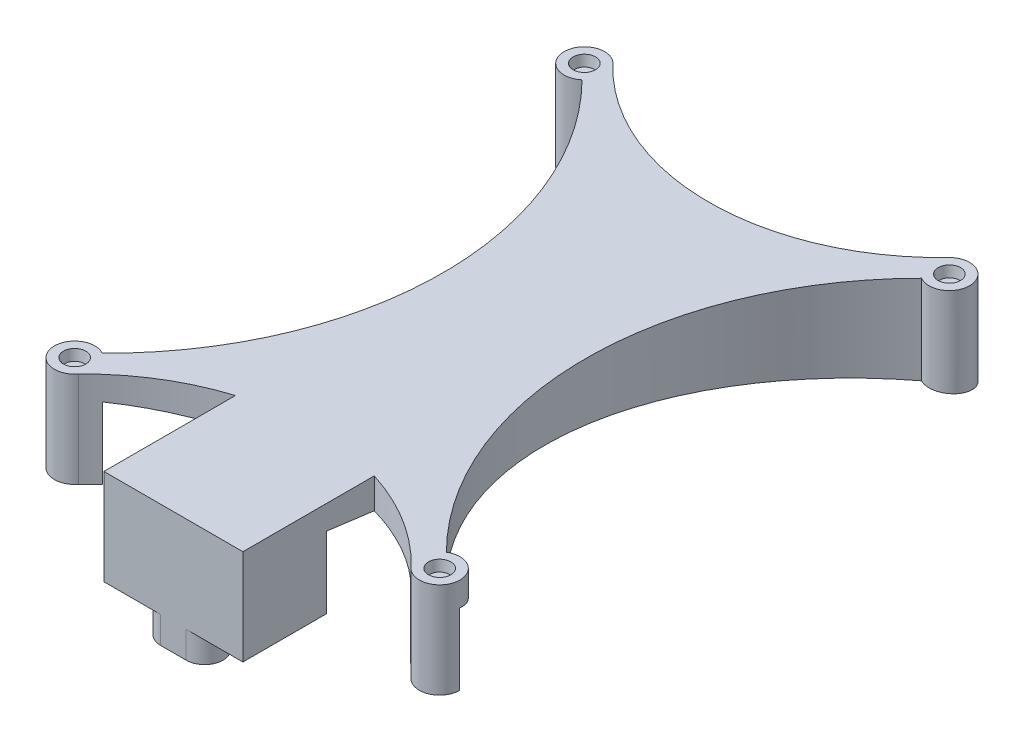
SolidWorks part; units mm, degrees
ref_plane "Front Plane" through (0, 0, 0) normal (0, 0, 1) x (1, 0, 0)
ref_plane "Top Plane" through (0, 0, 0) normal (0, 1, 0) x (1, 0, 0)
ref_plane "Right Plane" through (0, 0, 0) normal (1, 0, 0) x (0, 0, -1)
sketch "Sketch1" plane through (0, 0, 0) normal (0, 1, 0) x (1, 0, 0)
  line L2 (-16.4891, 8.3083) -> (-16.4891, -14.4005)
  line L3 (-16.4891, -14.4005) -> (7.5109, -14.4005)
  line L4 (7.5109, 8.2805) -> (7.5109, -14.4005)
  line L5 (-4.5332, -29.8631) -> (7.5109, -14.4005) construction
  line L6 (-16.4891, -14.4005) -> (-4.5332, -29.8631) construction
  circle A0 centre (-36.0381, 88.0995) radius 1.935 construction
  circle A1 centre (26.9839, 88.0995) radius 1.935 construction
  circle A2 centre (-36.0381, 0.0995) radius 1.935 construction
  circle A3 centre (26.9839, 0.0995) radius 1.935 construction
  arc A4 (-33.3739, 90.3693) -> (-33.7696, 85.4341) centre (-36.0381, 88.0995) ccw
  arc A5 (-34.3075, 3.1417) -> (-33.2563, -2.0247) centre (-36.0381, 0.0995) ccw
  arc A6 (25.1601, 3.0867) -> (24.2542, -2.0911) centre (26.9839, 0.0995) cw
  arc A7 (24.4703, 90.5349) -> (25.2108, 85.0818) centre (26.9839, 88.0995) cw
  arc A8 (-33.7696, 85.4341) -> (-34.3075, 3.1417) centre (-74.9145, 44.5551) cw
  arc A9 (25.2108, 85.0818) -> (25.1601, 3.0867) centre (66.2123, 44.0589) ccw
  arc A10 (-33.3739, 90.3693) -> (24.4703, 90.5349) centre (-4.5309, 118.0836) ccw
  arc A11 (-33.2563, -2.0247) -> (-16.4891, 8.3083) centre (-4.5332, -29.8631) cw
  arc A12 (7.5109, 8.2805) -> (24.2542, -2.0911) centre (-4.5332, -29.8631) cw
  point P20 (-4.5332, -29.8631)
  point P22 (-67.3528, 22.4953)
  point P24 (-4.1952, -32.0314)
  dimension "D2" = 3.87
  dimension "D3" = 24
  dimension "D5" = 3.5
  dimension "D6" = 3.5
  dimension "D7" = 3.5
  dimension "D8" = 3.5
  dimension "D11" = 58
  dimension "D12" = 58
  dimension "D13" = 40
  dimension "D14" = 40
  dimension "D10" = 63.022
  dimension "D16" = 14.5
extrude "Boss-Extrude1" add sketch "Sketch1" along normal blind 16.5
ref_plane "Plane1" through (35, 0, 0) normal (1, 0, 0) x (0, 0, -1)
sketch "Sketch2" plane through (35, 0, 0) normal (1, 0, 0) x (0, 0, -1)
  line L1 (0, 12.3611) -> (0, 0)
  line L5 (0, 0) -> (93.8921, 0)
  line L6 (93.8921, 0) -> (0, 12.3611)
  dimension "D1" = 7.5
extrude "Cut-Extrude1" cut sketch "Sketch2" against normal through all
sketch "Sketch4" plane through (0, 16.5, 0) normal (0, 1, 0) x (1, 0, 0)
  circle A0 centre (26.9839, 88.0995) radius 1.935
  circle A1 centre (-36.0381, 88.0995) radius 1.935
  circle A2 centre (-36.0381, 0.0995) radius 1.935
  circle A3 centre (26.9839, 0.0995) radius 1.935
  dimension "D3" = 3.87
  dimension "D4" = 3.87
  dimension "D5" = 3.87
  dimension "D6" = 3.87
  dimension "D1" = 63.022
  dimension "D2" = 88
extrude "Cut-Extrude2" cut sketch "Sketch4" against normal blind 1.7526 draft 8
sketch "Sketch9" plane through (0, 0, 0) normal (0, -1, 0) x (1, 0, 0)
  line L1 (2.9809, 14.4005) -> (-11.9591, 14.4005)
  line L2 (-16.4891, 14.4005) -> (7.5109, 14.4005) construction
  line L3 (-11.9591, 14.4005) -> (-4.4891, 0.1765)
  line L6 (-4.4891, 14.4005) -> (-4.4891, -5.7496) construction
  line L7 (2.9809, 14.4005) -> (-4.4891, 0.1765)
  dimension "D1" = 7.47
  dimension "D2" = 14.224
extrude "Boss-Extrude2" add sketch "Sketch9" along normal blind 4.6228
fillet "Fillet1" radius 3.175 3 edges at (-11.9591, -2.3114, 14.4005) (2.9809, -2.3114, 14.4005) (-4.4891, -2.3114, 0.1765)
